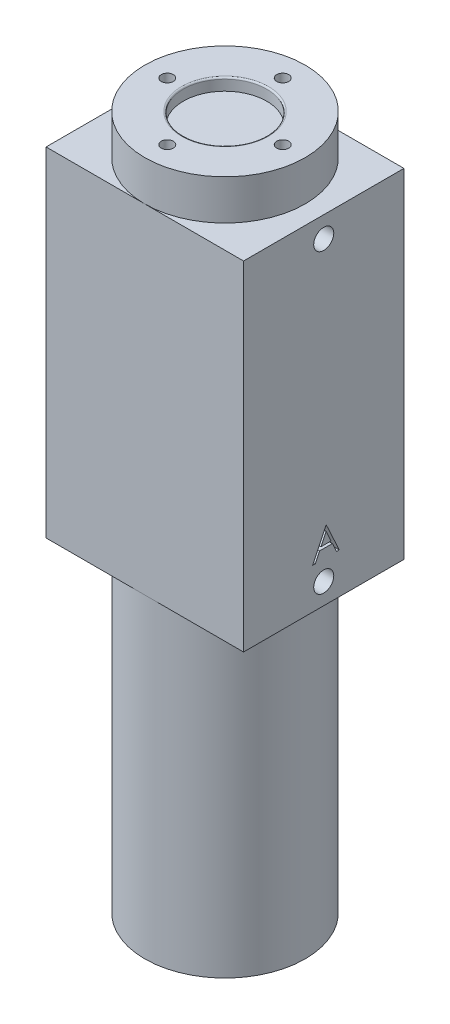
SolidWorks part; units mm, degrees
ref_plane "Front Plane" through (0, 0, 0) normal (0, 0, 1) x (1, 0, 0)
ref_plane "Top Plane" through (0, 0, 0) normal (0, 1, 0) x (1, 0, 0)
ref_plane "Right Plane" through (0, 0, 0) normal (1, 0, 0) x (0, 0, -1)
sketch "Sketch1" plane through (0, 0, 0) normal (1, 0, 0) x (0, 0, -1)
  line L2 (0, 0) -> (-30, 0)
  line L3 (-10.55, 7) -> (-10.55, 5)
  line L4 (-10.55, 5) -> (0, 5)
  line L5 (0, 5) -> (0, 0)
  line L6 (-10.55, 7) -> (-20.1025, 7)
  line L7 (-30, 0) -> (-30, 7)
  line L8 (-30, 7) -> (-20.1025, 7)
  dimension "D3" = 10.55
  dimension "D1" = 2
  dimension "D2" = 5
  dimension "D4" = 30
revolve "Revolve1" add sketch "Sketch1" angle 360 about L5
fillet "Fillet1" radius 1 1 edges at (0, 7, 10.55)
sketch "Sketch2" plane through (0, 5, 0) normal (0, 1, 0) x (1, 0, 0)
  circle A0 centre (0, 0) radius 5.2
  dimension "D1" = 10.4
extrude "Cut-Extrude1" cut sketch "Sketch2" against normal blind 1.5
fillet "Fillet2" radius 0.2 1 edges at (0, 5, 5.2)
fillet "Fillet3" radius 5 1 edges at (0, 7, 30)
ref_plane "Plane1" through (0, 0, 0) normal (0, -1, 0) x (-1, 0, 0)
sketch "Sketch4" plane through (0, 0, 0) normal (0, -1, 0) x (1, 0, 0)
  text T0 "1"
  text T1 "2"
  text T2 "3"
  text T3 "4"
extrude "Cut-Extrude2" cut sketch "Sketch4" against normal blind 1
sketch "Sketch5" plane through (0, 0, 0) normal (0, -1, 0) x (1, 0, 0)
  line L0 (0, -30) -> (0, 30)
  line L1 (-30, 0) -> (30, 0)
  circle A0 centre (0, 0) radius 30 construction
sketch "Sketch6" plane through (0, 0, 0) normal (0, -1, 0) x (1, 0, 0)
  circle A0 centre (0, 0) radius 10
  dimension "D1" = 20
extrude "Boss-Extrude1" add sketch "Sketch6" along normal blind 81.5333 contours A0
sketch "Sketch8" plane through (0, 0, 0) normal (0, -1, 0) x (-1, 0, 0)
  line L0 (0, 30) -> (0, -30) construction
  line L1 (-12.3137, 10) -> (12.3137, 10)
  line L2 (12.3137, 10) -> (12.3137, -10)
  line L3 (12.3137, -10) -> (-12.3137, -10)
  line L4 (0, 10) -> (0, -10.3766) construction
  line L5 (-12.3137, 10) -> (-12.3137, -10)
  arc A0 (0, 10) -> (0, -10) centre (0, 0) cw
  circle A1 centre (0, 0) radius 10 construction
  dimension "D1" = 12.3137
extrude "Boss-Extrude2" add sketch "Sketch8" along normal blind 45 from offset 2.77 contours L4 L1 L5 L3 | L1 A0 L3 L2 region at (6.1568, 0, 0) region at (-6.1568, 0, -9.7651) offset against normal yes
sketch "Sketch12" plane through (12.3137, 0, 0) normal (1, 0, 0) x (0, 0, -1)
  text T0 "A"
extrude "Cut-Extrude5" cut sketch "Sketch12" against normal blind 2
sketch "Sketch13" plane through (-12.3137, 0, 0) normal (-1, 0, 0) x (0, 0, 1)
  text T0 "B"
extrude "Cut-Extrude6" cut sketch "Sketch13" against normal blind 2
sketch "Sketch14" plane through (0, 0, 0) normal (0, -1, 0) x (1, 0, 0)
  circle A0 centre (0, 0) radius 10
extrude "Cut-Extrude-Thin1" cut sketch "Sketch14" against normal blind 10 thin contours A0 thin type one direction wall 30
sketch "Sketch29" plane through (0, 5, 0) normal (0, 1, 0) x (1, 0, 0)
  line L0 (0, 0) -> (-7.2, 0)
  line L1 (-30, 0) -> (30, 0) construction
  line L2 (0, 0) -> (0, 7.2)
  line L3 (0, 30) -> (0, -30) construction
  line L4 (0, 0) -> (7.2, 0)
  line L5 (0, 0) -> (0, -7.2)
  dimension "D1" = 7.2
  dimension "D2" = 7.2
  dimension "D3" = 7.2
  dimension "D4" = 7.2
hole_wizard "Ø1.5mm Dowel Hole1" positions "Sketch30" profile "Sketch31" hole size "Ø1.5" standard "ANSI Metric"
sketch "Sketch30" plane through (0, 5, 0) normal (0, 1, 0) x (1, 0, 0)
  point P0 (-7.2, 0)
  point P3 (0, 7.2)
  point P6 (7.2, 0)
  point P9 (0, -7.2)
sketch "Sketch31" plane through (-7.2, 5, 0) normal (1, 0, 0) x (0, 0, 1)
  line L0 (0, 0) -> (0, 12.4506)
  line L1 (0, 12.4506) -> (0.75, 12)
  line L2 (0.75, 12) -> (0.75, 0)
  line L5 (0.75, 0) -> (0, 0)
  line L10 (0, 12.4506) -> (-0.75, 12) construction
  line L11 (0, -6.35) -> (0, 107.95) construction
  dimension "Hole Dia." = 1.5
  dimension "Hole Depth" = 12
  dimension "Drill Angle" = 118
sketch "Sketch37" plane through (12.3137, 0, 0) normal (1, 0, 0) x (0, 0, -1)
  line L0 (0, -21.115) -> (0, -2.615)
  line L1 (0, -21.115) -> (0, -39.615)
  dimension "D1" = 18.5
  dimension "D2" = 18.5
hole_wizard "Ø2.5mm Dowel Hole1" positions "Sketch38" profile "Sketch39" hole size "Ø2.5" standard "ANSI Metric" end condition through all
sketch "Sketch38" plane through (12.3137, 0, 0) normal (1, 0, 0) x (0, 0, -1)
  point P0 (0, -2.615)
  point P3 (0, -39.615)
sketch "Sketch39" plane through (12.3137, -2.615, 0) normal (0, 1, 0) x (0, 0, -1)
  line L0 (0, 0) -> (0, 24.6273)
  line L1 (0, 24.6273) -> (1.25, 24.6273)
  line L2 (1.25, 24.6273) -> (1.25, 0)
  line L5 (1.25, 0) -> (0, 0)
  line L11 (0, -6.35) -> (0, 107.95) construction
  dimension "Thru Hole Dia." = 2.5
  dimension "Thru Hole Depth" = 24.6273
